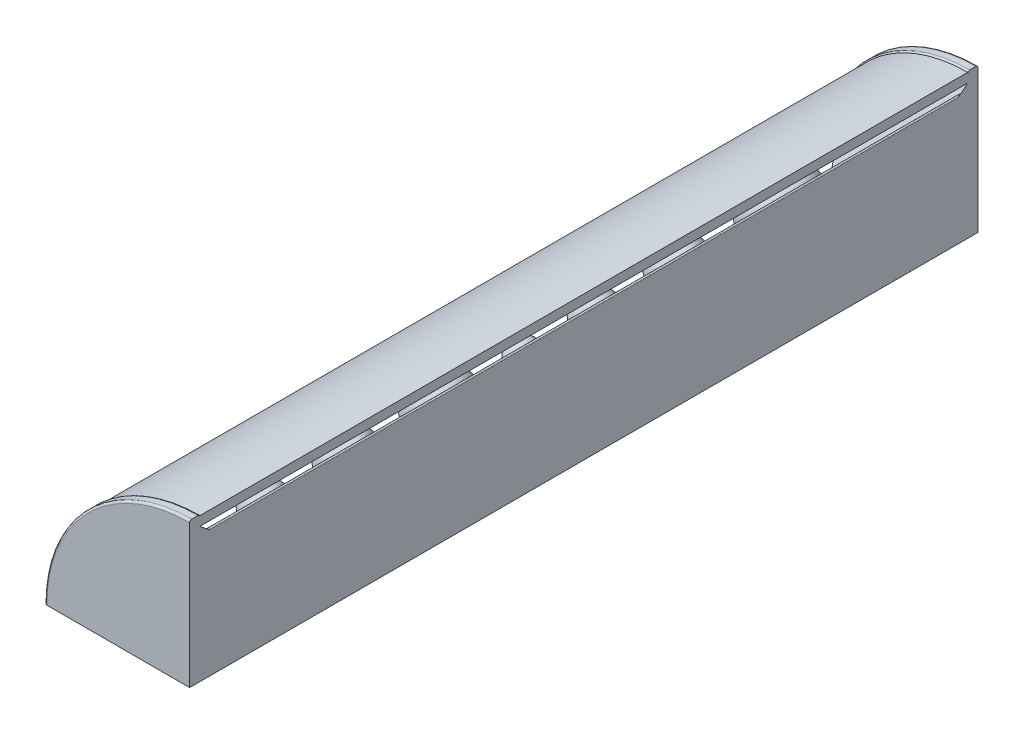
SolidWorks part; units mm, degrees
ref_plane "Front Plane" through (0, 0, 0) normal (0, 0, 1) x (1, 0, 0)
ref_plane "Top Plane" through (0, 0, 0) normal (0, 1, 0) x (1, 0, 0)
ref_plane "Right Plane" through (0, 0, 0) normal (1, 0, 0) x (0, 0, -1)
sketch "Sketch2" plane through (0, 0, 0) normal (0, 0, 1) x (1, 0, 0)
  line L0 (0, 17.78) -> (0, 0)
  line L1 (0, 0) -> (-17.78, 0)
  arc A0 (-17.78, 0) -> (0, 17.78) centre (0, 0) cw
  arc A1 (-16.51, 0) -> (0, 16.51) centre (0, 0) cw construction
  dimension "D1" = 17.78
  dimension "D2" = 16.51
extrude "Boss-Extrude1" add sketch "Sketch2" against normal blind 1.27
sketch "Sketch4" plane through (0, 0, -1.27) normal (0, 0, -1) x (-1, 0, 0)
  line L0 (0, 16.51) -> (0, 0)
  line L1 (0, 0) -> (16.51, 0)
  arc A0 (0, 16.51) -> (16.51, 0) centre (0, 0) cw
extrude "Boss-Extrude2" add sketch "Sketch4" along normal blind 94.234
ref_plane "Plane1" through (0, 0, -48.387) normal (0, 0, -1) x (-1, 0, 0)
mirror "Mirror1" about plane through (0, 0, -48.387) normal (0, 0, -1) of "Boss-Extrude1"
fillet "Fillet1" radius 0.254 4 edges at (-12.5724, 12.5724, -1.27) (-12.5724, 12.5724, -95.504) (-12.5724, 12.5724, 0) (-12.5724, 12.5724, -96.774)
ref_plane "Plane2" through (-8.255, 8.255, 0) normal (-0.7071, 0.7071, 0) x (0.7071, 0.7071, 0)
sketch "Sketch5" plane through (-8.255, 8.255, 0) normal (-0.7071, 0.7071, 0) x (0.7071, 0.7071, 0)
  line L1 (-11.6743, 95.504) -> (11.6743, 95.504)
  line L2 (-11.6743, 95.504) -> (-11.6743, 1.27)
  line L3 (-11.6743, 1.27) -> (11.6743, 1.27)
  line L4 (11.6743, 95.504) -> (11.6743, 1.27)
extrude "Cut-Extrude1" cut sketch "Sketch5" along normal blind 12.7 and the other way blind 5.08 draft 60
fillet "Fillet2" radius 0.127 2 edges
sketch "Sketch6" plane through (-4.6629, 4.6629, 0) normal (-0.7071, 0.7071, 0) x (0, 0, 1)
  line L0 (-86.7052, 0) -> (-10.0688, 0) construction
  line L1 (-86.7052, 2.8755) -> (-86.7052, -2.8755) construction
  line L2 (-10.0688, -2.8755) -> (-10.0688, 2.8755) construction
  circle A0 centre (-48.387, 0) radius 3.81
  circle A1 centre (-38.227, 0) radius 5.715
  circle A2 centre (-26.797, 0) radius 5.08
  circle A3 centre (-16.637, 0) radius 4.445
  circle A4 centre (-57.277, 0) radius 4.445
  circle A5 centre (-67.437, 0) radius 5.08
  circle A6 centre (-80.137, 0) radius 6.35
  dimension "D2" = 12.7
  dimension "D3" = 10.16
  dimension "D6" = 8.89
  dimension "D7" = 7.62
  dimension "D9" = 11.43
  dimension "D11" = 10.16
  dimension "D12" = 8.89
  dimension "D1" = 8.89
  dimension "D4" = 12.7
  dimension "D5" = 10.16
  dimension "D8" = 10.16
  dimension "D10" = 11.43
  dimension "D13" = 10.16
extrude "Boss-Extrude3" add sketch "Sketch6" along normal blind 3.81
fillet "Fillet3" radius 1.27 7 edges at (-10.5001, 4.2139, -16.637) (-10.9491, 3.7649, -26.797) (-11.3981, 3.3159, -38.227) (-10.0511, 4.6629, -48.387) (-10.5001, 4.2139, -57.277) (-10.9491, 3.7649, -67.437) (-11.8471, 2.8668, -80.137)
sketch "Sketch7" plane through (-7.357, 7.357, 0) normal (-0.7071, 0.7071, 0) x (0, 0, 1)
  line L0 (-85.217, 0) -> (-13.462, 0) construction
  line L1 (-84.582, 0) -> (-75.692, 0)
  line L2 (-70.612, 0) -> (-64.262, 0)
  line L3 (-59.817, 0) -> (-54.737, 0)
  line L4 (-50.292, 0) -> (-46.482, 0)
  line L5 (-42.037, 0) -> (-34.417, 0)
  line L6 (-34.417, 0) -> (-34.4719, 0.0202)
  line L7 (-29.972, 0) -> (-23.622, 0)
  line L8 (-19.177, 0) -> (-14.097, 0)
  circle A0 centre (-80.137, 0) radius 5.08 construction
  circle A1 centre (-16.637, 0) radius 3.175 construction
  arc A2 (-84.582, 0) -> (-75.692, 0) centre (-80.137, 0) cw
  arc A3 (-70.612, 0) -> (-64.262, 0) centre (-67.437, 0) cw
  arc A4 (-59.817, 0) -> (-54.737, 0) centre (-57.277, 0) cw
  arc A5 (-50.292, 0) -> (-46.482, 0) centre (-48.387, 0) cw
  arc A6 (-42.037, 0) -> (-34.417, 0) centre (-38.227, 0) cw
  arc A7 (-29.972, 0) -> (-23.622, 0) centre (-26.797, 0) ccw
  arc A8 (-19.177, 0) -> (-14.097, 0) centre (-16.637, 0) ccw
  circle A9 centre (-67.437, 0) radius 3.81 construction
  circle A10 centre (-57.277, 0) radius 3.175 construction
  circle A11 centre (-48.387, 0) radius 2.54 construction
  circle A12 centre (-38.227, 0) radius 4.445 construction
  circle A13 centre (-26.797, 0) radius 3.81 construction
  dimension "D1" = 0.635
  dimension "D2" = 0.635
  dimension "D3" = 0.635
  dimension "D4" = 0.635
  dimension "D5" = 0.635
  dimension "D6" = 0.635
  dimension "D7" = 0.635
revolve "Revolve1" add sketch "Sketch7" angle 360 about L0 region at (-6.023, 8.6909, -80.137) region at (-6.4041, 8.3098, -67.437) region at (-6.5947, 8.1192, -57.277) region at (-6.7853, 7.9287, -48.387) region at (-6.2136, 8.5004, -38.227) region at (-8.3098, 6.4041, -26.797) region at (-8.1192, 6.5947, -16.637)
sketch "Sketch8" plane through (0, 0, -95.504) normal (0, 0, 1) x (1, 0, 0)
  line L0 (-16.51, 0) -> (0, 16.51) construction
  line L1 (-0.6482, 15.8618) -> (0, 16.51)
  line L2 (0, 16.51) -> (0, 17.653)
  line L3 (0, 17.526) -> (0, 17.78) construction
  line L4 (-15.8618, 0.6482) -> (-16.51, 0)
  line L5 (-16.51, 0) -> (-17.653, 0)
  line L6 (-17.78, 0) -> (-17.526, 0) construction
  arc A0 (-15.8618, 0.6482) -> (-0.6482, 15.8618) centre (0, 0) cw
  arc A1 (-17.653, 0) -> (0, 17.653) centre (0, 0) cw
  dimension "D1" = 15.875
extrude "Boss-Extrude4" add sketch "Sketch8" along normal blind 94.234
